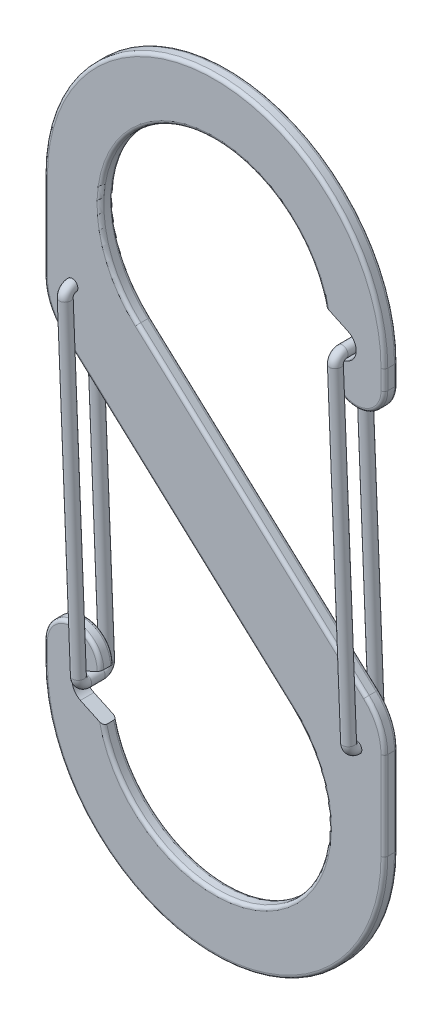
SolidWorks part; units mm, degrees
ref_plane "Front Plane" through (0, 0, 0) normal (0, 0, 1) x (1, 0, 0)
ref_plane "Top Plane" through (0, 0, 0) normal (0, 1, 0) x (1, 0, 0)
ref_plane "Right Plane" through (0, 0, 0) normal (1, 0, 0) x (0, 0, -1)
sketch "Sketch1" plane through (0, 0, 0) normal (0, 0, 1) x (1, 0, 0)
  line L0 (-8.9917, 14.9176) -> (7.3454, 0)
  line L1 (13.335, 24.765) -> (13.335, 19.17)
  line L2 (22.0363, 0) -> (-7.3454, 0) construction
  line L3 (7.3454, 0) -> (7.3454, -42.7213) construction
  line L4 (-19.939, 24.765) -> (-19.939, 11.4993)
  line L5 (-19.939, 11.4993) -> (-7.3454, 0)
  line L6 (13.335, 19.17) -> (19.939, 19.17)
  line L7 (19.939, 19.17) -> (19.939, 24.765)
  line L8 (-7.3454, 0) -> (-0.6659, 7.3152) construction
  line L9 (-7.3454, 0) -> (7.3454, 0)
  arc A0 (-13.335, 24.765) -> (13.335, 24.765) centre (0, 24.765) cw
  arc A1 (-19.939, 24.765) -> (19.939, 24.765) centre (0, 24.765) cw
  arc A2 (-13.335, -24.765) -> (13.335, -24.765) centre (0, -24.765) ccw construction
  arc A3 (-13.335, 24.765) -> (-8.9917, 14.9176) centre (0, 24.765) ccw
  arc A4 (13.335, 22.472) -> (19.939, 22.472) centre (16.637, 22.472) ccw
  arc A5 (-19.939, -24.765) -> (19.939, -24.765) centre (0, -24.765) ccw construction
  dimension "D2" = 13.335
  dimension "Thickness" = 6.604
  dimension "Usable Length" = 76.2
  dimension "D3" = 9.906
  dimension "Inside Width" = 26.67
  dimension "Opening Width" = 19.558
extrude "Boss-Extrude1" add sketch "Sketch1" along normal mid plane 1.5875 contours A3 A0 L1 L6 L7 A1 L4 L5 L9 L0 region at (-1.2271, 7.0164, 0)
sketch "Sketch2" plane through (0, 0, 0) normal (0, 0, 1) x (1, 0, 0)
  line L0 (-19.939, 11.4993) -> (-16.637, 15.1155) construction
  line L1 (-16.637, 15.1155) -> (-13.335, 18.7317) construction
  line L2 (-13.335, 18.7317) -> (-13.335, 24.765) construction
  line L3 (16.637, 22.472) -> (16.637, 25.0636) construction
  line L4 (14.986, 25.0636) -> (13.3317, 25.0636) construction
  line L5 (0, 33.8734) -> (0, 16.2538)
  line L6 (0, 33.8734) -> (15.6837, 26.5599)
  line L7 (-19.939, 11.4993) -> (-7.3454, 0) construction
  line L8 (0, 16.2538) -> (15.6837, 23.5673)
  line L10 (13.335, 24.765) -> (13.335, 22.472) construction
  circle A0 centre (14.986, 25.0636) radius 1.651
  circle A1 centre (-16.637, 15.1155) radius 0.6604
  arc A2 (13.335, 24.765) -> (-8.9917, 14.9176) centre (0, 24.765) ccw construction
  arc A3 (13.3317, 25.0636) -> (-8.9917, 14.9176) centre (0, 24.765) ccw construction
  arc A4 (13.335, 22.472) -> (19.939, 22.472) centre (16.637, 22.472) ccw construction
  arc A5 (13.335, 22.472) -> (19.939, 22.472) centre (16.637, 22.472) ccw construction
  dimension "D1" = 1.3208
  dimension "D4" = 25
  dimension "D3" = 5.8936
extrude "Cut-Extrude1" cut sketch "Sketch2" against normal through all both and the other way through all contours A1 | A0 | A0 L6 L5 | A0 L5 region at (5.6234, 25.0636, 0) region at (14.986, 25.0636, 0) region at (-16.637, 15.1155, 0)
fillet "Fillet1" radius 6.6675 1 edges at (-19.939, 11.4993, 0)
fillet "Fillet2" radius 0.3969 16 edges at (-0.8231, 7.4588, -0.7937) (16.637, 19.17, -0.7937) (19.939, 23.6185, -0.7937) (0, 44.704, -0.7937) (-19.939, 19.6025, -0.7937) (-19.372, 11.7494, -0.7937) (-0.8231, 7.4588, 0.7937) (16.637, 19.17, 0.7937) (19.939, 23.6185, 0.7937) (0, 44.704, 0.7937) (-19.939, 19.6025, 0.7937) (-19.372, 11.7494, 0.7937) (-6.7527, 36.2638, -0.7937) (-12.5564, 4.7582, -0.7937) (-6.7527, 36.2638, 0.7937) (-12.5564, 4.7582, 0.7937)
mirror "Mirror1" about plane through (0, 0, 0.7937) normal (0, 1, 0) of bodies 313 309
mirror "Mirror2" about plane through (0, 0, 0) normal (1, 0, 0) of bodies 310
combine bodies "Combine1" operation type add bodies to combine 313 311
ref_plane "Plane1" through (-15.9889, -0.657, 0) normal (0.9992, 0.0411, 0) x (0, 0, -1)
sketch "Sketch3" plane through (-15.9889, -0.657, 0) normal (0.9992, 0.0411, 0) x (0, 0, -1)
  line L0 (-0.7937, 16.4462) -> (-0.7937, 15.1254) construction
  line L1 (-0.7937, 16.4462) -> (-0.7937, 15.1254) construction
  line L2 (-0.7937, -22.9035) -> (-0.7937, -25.8936) construction
  line L3 (-0.7937, -22.9035) -> (-0.7937, -25.8936) construction
  line L4 (0, -24.3985) -> (-0.7937, -24.3985) construction
  line L5 (0, -24.3985) -> (0, 15.7858) construction
  line L6 (0, 15.7858) -> (-0.7937, 15.7858) construction
  line L7 (0.7937, 15.1254) -> (-0.7937, 15.1254)
  line L8 (-0.9922, 14.927) -> (-0.9922, -22.7051)
  line L9 (-0.7937, 15.2742) -> (-0.7937, -10.2378) construction
  line L10 (0.9922, 14.927) -> (0.9922, -22.7051)
  line L11 (-0.7937, -22.9035) -> (0.7937, -22.9035)
  arc A0 (-0.7937, 15.1254) -> (-0.9922, 14.927) centre (-0.7937, 14.927) ccw
  arc A1 (-0.9922, -22.7051) -> (-0.7937, -22.9035) centre (-0.7937, -22.7051) ccw
  arc A2 (0.9922, -22.7051) -> (0.7937, -22.9035) centre (0.7937, -22.7051) cw
  arc A3 (0.7937, 15.1254) -> (0.9922, 14.927) centre (0.7937, 14.927) cw
  point P22 (0, 15.1254)
  dimension "D3" = 0.1984
  dimension "D1" = 2.9901
  dimension "D2" = 1.3208
sketch "Sketch4" plane through (0, 0, 0.7937) normal (0, 0, 1) x (1, 0, 0)
  circle A0 centre (-16.637, 15.1155) radius 0.6604 construction
  circle A1 centre (-16.637, 15.1155) radius 0.6604
sweep "Sweep1" add profiles "Sketch4" path "Sketch3"
mirror "Mirror3" about plane through (0, 0, 0) normal (1, 0, 0) of bodies 314
mirror "Mirror4" about plane through (0, 0, 0) normal (0, 1, 0) of bodies 317
delete or keep bodies "Body-Delete1" type delete bodies bodies 310 317
equation "\"3..6250in\"=4.625"
equation "\"D2@Sketch1\"=\"Inside Width@Sketch1\"/2"
equation "\"D3@Sketch1\"=\"Thickness@Sketch1\"*1.5"
equation "\"D1@Fillet1\"=\"D2@Sketch1\"/2"
equation "\"D1@Sketch2\"=\"Thickness@Sketch1\"/5"
